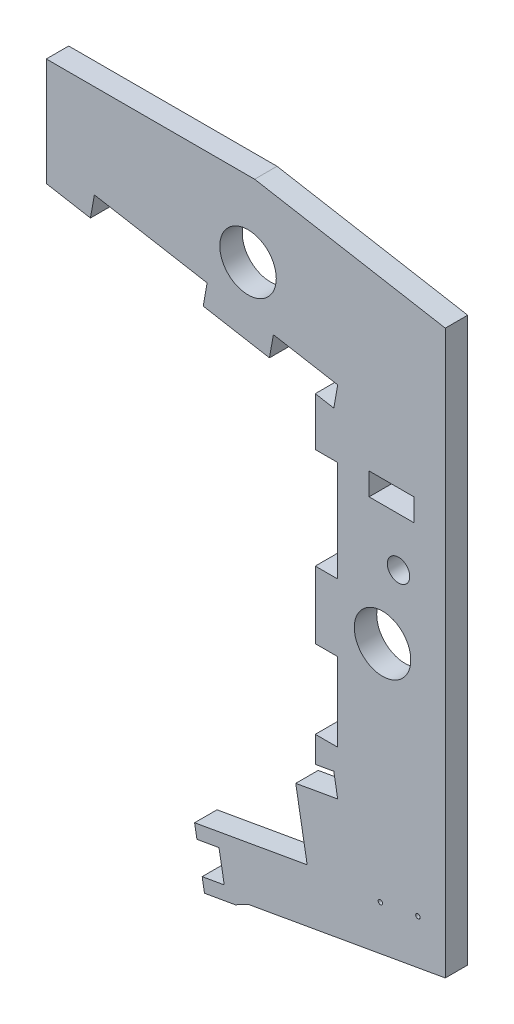
SolidWorks part; units mm, degrees
material "Balsa"
ref_plane "Plan de face" through (0, 0, 0) normal (0, 0, 1) x (1, 0, 0)
ref_plane "Plan de dessus" through (0, 0, 0) normal (0, 1, 0) x (1, 0, 0)
ref_plane "Plan de droite" through (0, 0, 0) normal (1, 0, 0) x (0, 0, -1)
sketch "Esquisse1" plane through (0, 0, 0) normal (0, 0, 1) x (1, 0, 0)
  line L0 (-65, 51.4613) -> (0, 40)
  line L1 (0, 40) -> (0, -40)
  line L2 (-6.8091, -56.1122) -> (-9.3591, -41.6503)
  line L3 (-9.3591, -41.6503) -> (0, -40)
  line L4 (-6.8091, -56.1122) -> (-31.9182, -60.5396)
  line L5 (-29.71, -73.063) -> (25, -63.4162)
  line L6 (25, -63.4162) -> (25, 63.8008)
  line L7 (25, 63.8008) -> (-18.4444, 71.4613)
  line L8 (-65, 71.4613) -> (-65, 51.4613)
  line L10 (-31.9182, -60.5396) -> (-29.71, -73.063)
  line L11 (-18.4444, 71.4613) -> (-65, 71.4613)
  line L12 (-18.4444, 71.4613) -> (-20, 53.6808) construction
  circle A0 centre (-20, 53.6808) radius 6.3
  circle A1 centre (10, -5) radius 6.3
  circle A2 centre (13.572, 11) radius 2.5
  point P4 (-29.6197, 71.4613)
  point P19 (-7.4389, 69.5207)
  point P24 (17.5577, -5.2313)
  point P25 (28.2643, 8.6297)
  dimension "D1" = 12.6
  dimension "D15" = 12.6
  dimension "D22" = 5
  dimension "D2" = 10
  dimension "D3" = 20
  dimension "D4" = 80
  dimension "D5" = 65
  dimension "D6" = 100
  dimension "D7" = 100
  dimension "D8" = 85
  dimension "D9" = 35
  dimension "D10" = 90
  dimension "D11" = 9.5035
  dimension "D12" = 14.685
  dimension "D13" = 10
  dimension "D14" = 35
  dimension "D16" = 12.7166
  dimension "D17" = 100
  dimension "D18" = 100
  dimension "D19" = 20
  dimension "D20" = 13.572
  dimension "D21" = 16
extrude "Boss.-Extru.1" add sketch "Esquisse1" along normal blind 5
sketch "Esquisse2" plane through (0, 0, 0) normal (0, 0, -1) x (-1, 0, 0)
  line L0 (31.3966, -63.498) -> (30.231, -70.1086)
  line L1 (31.3966, -63.498) -> (26.4726, -62.6297)
  line L2 (30.231, -70.1086) -> (25.3069, -69.2404)
  line L3 (26.4726, -62.6297) -> (25.3069, -69.2404)
  line L5 (-16.8787, -72.4038) -> (-12.3995, -47.0007) construction
  line L6 (-17, 26.8717) -> (-7, 26.8717)
  line L7 (-17, 26.8717) -> (-17, 21.8717)
  line L8 (-17, 21.8717) -> (-7, 21.8717)
  line L9 (-7, 26.8717) -> (-7, 21.8717)
  line L11 (31.9182, -60.5396) -> (29.71, -73.063) construction
  line L12 (6.8091, -56.1122) -> (31.9182, -60.5396) construction
  circle A0 centre (-9.5242, -55.1691) radius 0.5
  circle A1 centre (-17.8951, -53.6931) radius 0.5
  dimension "D2" = 5
  dimension "D3" = 3.004
  dimension "D4" = 3
extrude "Enlèv. mat.-Extru.1" cut sketch "Esquisse2" against normal blind 5
sketch "Esquisse3" plane through (0, 0, 0) normal (0, 0, 1) x (1, 0, 0)
  line L0 (0, -40) -> (0, -30)
  line L1 (0, 40) -> (0, -40) construction
  line L2 (0, -40) -> (-9.3591, -41.6503) construction
  line L3 (0, -30) -> (-5, -30)
  line L4 (-5, -30) -> (-5, -35.8045)
  line L5 (-5, -35.8045) -> (-0.8682, -35.076)
  line L6 (-0.8682, -35.076) -> (0, -40)
  line L7 (0, 0) -> (-23.4139, 0) construction
  line L8 (0, 2.5) -> (-5, 2.5)
  line L9 (0, 2.5) -> (0, -12.5)
  line L10 (0, -12.5) -> (-5, -12.5)
  line L11 (-5, 2.5) -> (-5, -12.5)
  line L12 (0, 40) -> (0, -40) construction
  line L13 (-0.8682, 35.076) -> (0, 40)
  line L14 (-5, 35.8045) -> (-0.8682, 35.076)
  line L15 (-5, 25) -> (-5, 35.8045)
  line L16 (0, 25) -> (-5, 25)
  line L17 (0, 40) -> (0, 25)
  line L18 (-29.1225, 45.1351) -> (-14.3504, 42.5304)
  line L19 (-65, 51.4613) -> (0, 40) construction
  line L20 (-14.3504, 42.5304) -> (-15.2187, 37.6063)
  line L21 (-15.2187, 37.6063) -> (-29.9908, 40.2111)
  line L22 (-29.9908, 40.2111) -> (-29.1225, 45.1351)
  line L23 (-65, 51.4613) -> (-65, 46.3841)
  line L24 (-65, 46.3841) -> (-55.1519, 44.6476)
  line L25 (-55.1519, 44.6476) -> (-54.2837, 49.5717)
  line L26 (-54.2837, 49.5717) -> (-65, 51.4613)
  line L27 (-65, 71.4613) -> (-65, 51.4613) construction
  circle A0 centre (10, -5) radius 6.3 construction
  circle A1 centre (-20, 53.6808) radius 6.3 construction
  dimension "D1" = 10
  dimension "D2" = 5
  dimension "D3" = 5
  dimension "D4" = 10
  dimension "D5" = 5
  dimension "D6" = 7.5
  dimension "D7" = 15
  dimension "D8" = 15
  dimension "D9" = 5
  dimension "D10" = 15
  dimension "D11" = 7.5
  dimension "D12" = 5
  dimension "D13" = 10
extrude "Boss.-Extru.3" add sketch "Esquisse3" along normal blind 5
sketch "Esquisse4" plane through (0, 0, 5) normal (0, 0, 1) x (1, 0, 0)
  line L0 (-65, 70.4613) -> (-18.5319, 70.4613)
  line L1 (-65, 71.4613) -> (-65, 46.3841) construction
  line L2 (-18.5319, 70.4613) -> (24, 62.9617)
  line L3 (24, 62.9617) -> (24, -62.5771)
  line L4 (24, -62.5771) -> (-19.8968, -70.3173)
  line L5 (-19.8968, -70.3173) -> (-22.8293, -71.8498)
  line L6 (-29.71, -73.063) -> (25, -63.4162) construction
  line L7 (-65, 70.4613) -> (-65, 79.0214)
  line L8 (-65, 79.0214) -> (35.2298, 79.0214)
  line L9 (35.2298, 79.0214) -> (35.2298, -71.8498)
  line L10 (35.2298, -71.8498) -> (-22.8293, -71.8498)
  line L11 (-18.4444, 71.4613) -> (-65, 71.4613) construction
  line L12 (25, 63.8008) -> (-18.4444, 71.4613) construction
  line L13 (25, -63.4162) -> (25, 63.8008) construction
  dimension "D1" = 1
  dimension "D2" = 1
  dimension "D3" = 1
  dimension "D4" = 1
extrude "Enlèv. mat.-Extru.2" cut sketch "Esquisse4" against normal blind 5
